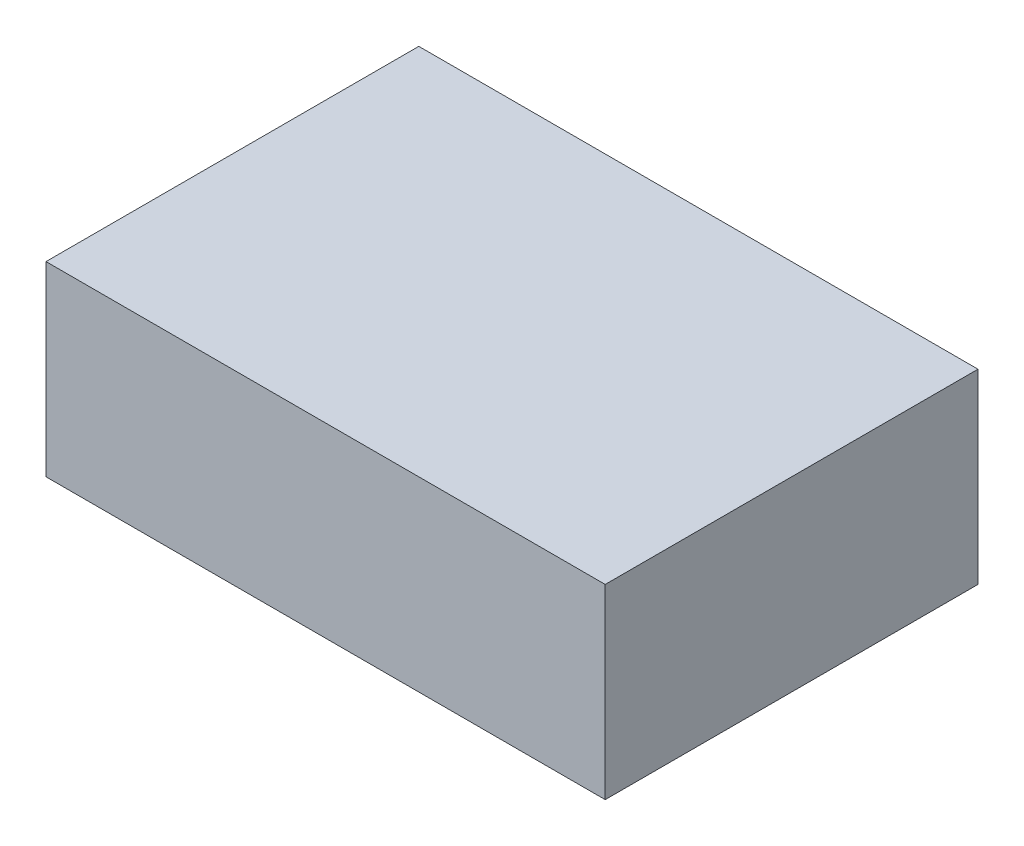
SolidWorks part; units mm, degrees
ref_plane "Front Plane" through (0, 0, 0) normal (0, 0, 1) x (1, 0, 0)
ref_plane "Top Plane" through (0, 0, 0) normal (0, 1, 0) x (1, 0, 0)
ref_plane "Right Plane" through (0, 0, 0) normal (1, 0, 0) x (0, 0, -1)
sketch "Sketch1" plane through (0, 0, 0) normal (0, 1, 0) x (1, 0, 0)
  line L1 (-38.1, 25.4) -> (38.1, 25.4)
  line L2 (-38.1, 25.4) -> (-38.1, -25.4)
  line L3 (-38.1, -25.4) -> (38.1, -25.4)
  line L4 (38.1, 25.4) -> (38.1, -25.4)
  line L5 (-38.1, 25.4) -> (38.1, -25.4) construction
  line L6 (-38.1, -25.4) -> (38.1, 25.4) construction
  point P0 (0, 0)
  dimension "D1" = 50.8
  dimension "D2" = 76.2
extrude "Boss-Extrude1" add sketch "Sketch1" along normal blind 25.4
